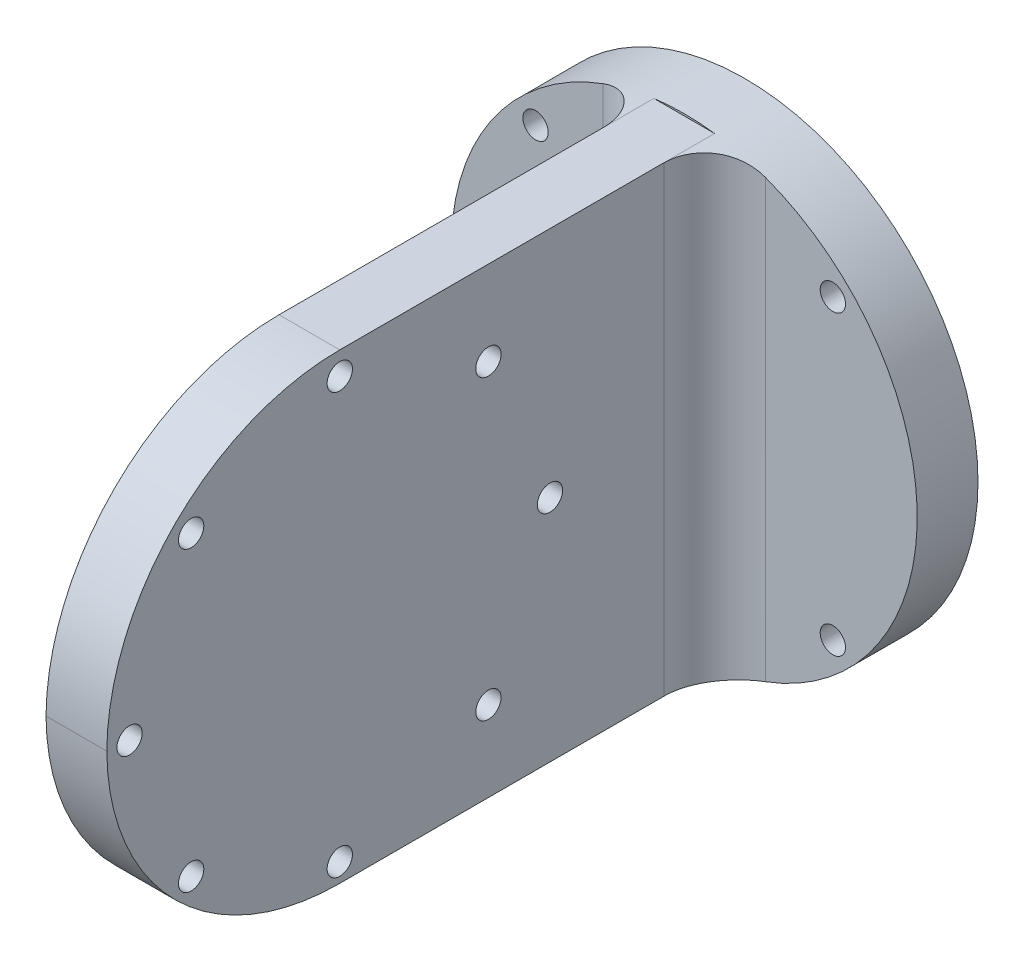
SolidWorks part; units mm, degrees
ref_plane "Front Plane" through (0, 0, 0) normal (0, 0, 1) x (1, 0, 0)
ref_plane "Top Plane" through (0, 0, 0) normal (0, 1, 0) x (1, 0, 0)
ref_plane "Right Plane" through (0, 0, 0) normal (1, 0, 0) x (0, 0, -1)
sketch "Sketch2" plane through (0, 0, 0) normal (0, 0, 1) x (1, 0, 0)
  circle A0 centre (0, 0) radius 46
  dimension "D1" = 92
extrude "Boss-Extrude1" add sketch "Sketch2" along normal blind 12
sketch "Sketch3" plane through (0, 0, 12) normal (0, 0, 1) x (1, 0, 0)
  line L1 (-6, 45.607) -> (6, 45.607)
  line L2 (-6, 45.607) -> (-6, -45.607)
  line L3 (-6, -45.607) -> (6, -45.607)
  line L4 (6, 45.607) -> (6, -45.607)
  line L5 (-6, 45.607) -> (6, -45.607) construction
  line L6 (-6, -45.607) -> (6, 45.607) construction
  circle A0 centre (0, 0) radius 46 construction
  arc A1 (6, 45.607) -> (-6, 45.607) centre (0, 0) ccw
  arc A2 (-6, -45.607) -> (6, -45.607) centre (0, 0) ccw
  point P0 (0, 0)
  dimension "D1" = 12
  dimension "D2" = 91.214
extrude "Boss-Extrude2" add sketch "Sketch3" along normal blind 120 contours L4 L1 L2 L3 region at (0, 0, 12)
fillet "Fillet1" radius 10 2 edges at (6, 0, 12) (-6, 0, 12)
sketch "Sketch4" plane through (0, 0, 0) normal (0, 0, -1) x (-1, 0, 0)
  circle A2 centre (29.3449, 29.3449) radius 2.5
  circle A4 centre (29.3449, -29.3449) radius 2.5
  circle A6 centre (-29.3449, -29.3449) radius 2.5
  circle A8 centre (-29.3449, 29.3449) radius 2.5
  point P21 (0, 0)
extrude "Cut-Extrude1" cut sketch "Sketch4" against normal blind 100
fillet "Fillet2" radius 46 2 edges at (0, -45.607, 132) (0, 45.607, 132)
sketch "Sketch5" plane through (6, 0, 0) normal (1, 0, 0) x (0, 0, -1)
  circle A1 centre (-127.5, -0.393) radius 2.5
  circle A2 centre (-115.3449, 28.9519) radius 2.5
  circle A3 centre (-86, 41.107) radius 2.5
  circle A4 centre (-56.6551, 28.9519) radius 2.5
  circle A5 centre (-44.5, -0.393) radius 2.5
  circle A6 centre (-56.6551, -29.7379) radius 2.5
  circle A7 centre (-86, -41.893) radius 2.5
  circle A8 centre (-115.3449, -29.7379) radius 2.5
  point P21 (-86, -0.393)
  dimension "D2" = 5
  dimension "D3" = 8
extrude "Cut-Extrude2" cut sketch "Sketch5" against normal blind 100
